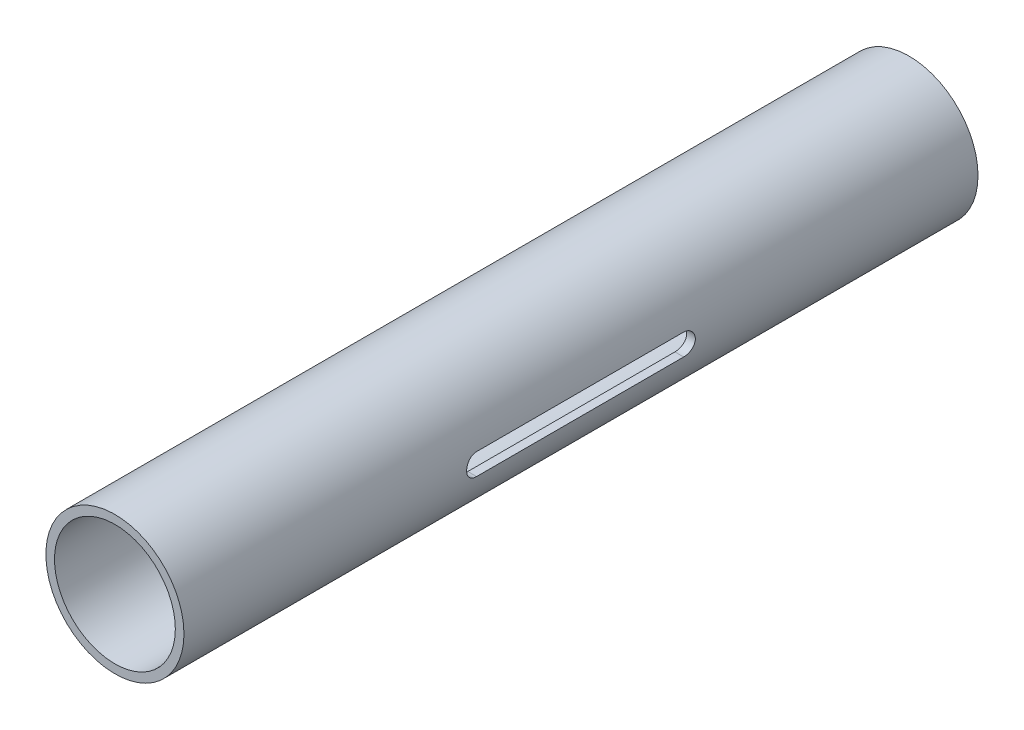
SolidWorks part; units mm, degrees
ref_plane "Front Plane" through (0, 0, 0) normal (0, 0, 1) x (1, 0, 0)
ref_plane "Top Plane" through (0, 0, 0) normal (0, 1, 0) x (1, 0, 0)
ref_plane "Right Plane" through (0, 0, 0) normal (1, 0, 0) x (0, 0, -1)
sketch "Sketch1" plane through (0, 0, 0) normal (0, 0, 1) x (1, 0, 0)
  line L0 (-25.4, 0) -> (-22.225, 0) construction
  circle A0 centre (0, 0) radius 22.225 construction
  circle A1 centre (0, 0) radius 25.4 construction
  dimension "OD" = 50.8
  dimension "ID" = 44.45
  dimension "Wall Thickness" = 3.175
sketch "Sketch2" plane through (0, 0, 0) normal (1, 0, 0) x (0, 0, -1)
  line L0 (-152.4, -25.4) -> (152.4, -25.4) construction
  point P2 (0, -25.4)
  point P3 (76.2, -25.4)
  point P4 (-76.2, -25.4)
  dimension "Length" = 304.8
  dimension "D1" = 76.2
  dimension "D2" = 76.2
sketch "Sketch3" plane through (0, 0, 0) normal (0, 0, 1) x (1, 0, 0)
  circle A0 centre (0, 0) radius 22.225 construction
  circle A1 centre (0, 0) radius 25.4 construction
  circle A2 centre (0, 0) radius 22.225
  circle A3 centre (0, 0) radius 25.4
extrude "Boss-Extrude2" add sketch "Sketch3" along normal up to vertex (152.4 mm away) and the other way up to vertex (152.4 mm away) up to point (0, -25.4, 152.4) other way up to point (0, -25.4, -152.4)
sketch "Sketch4" plane through (0, 0, 152.4) normal (0, 0, 1) x (1, 0, 0)
  circle A0 centre (0, 0) radius 36.4857
extrude "Cut-Extrude1" cut sketch "Sketch4" against normal offset from surface (12.7 mm away) 12.7 up to face at (25.4, 0, 152.4)
sketch "Sketch5" plane through (0, 0, 0) normal (1, 0, 0) x (0, 0, -1)
  line L0 (6.35, 0) -> (44.45, 0) construction
  line L1 (6.35, 0) -> (-31.75, 0) construction
  line L2 (-139.7, 0) -> (152.4, 0) construction
  line L3 (152.4, -25.4) -> (152.4, 25.4) construction
  line L4 (-139.7, 25.4) -> (-139.7, -25.4) construction
  line L5 (-31.75, 3.9687) -> (44.45, 3.9687)
  line L6 (44.45, -3.9687) -> (-31.75, -3.9687)
  line L7 (6.35, 3.9687) -> (6.35, -3.9687) construction
  circle A0 centre (-31.75, 0) radius 3.9687 construction
  arc A2 (-31.75, 3.9687) -> (-31.75, -3.9687) centre (-31.75, 0) ccw
  circle A4 centre (44.45, 0) radius 3.9688 construction
  arc A5 (44.45, 3.9687) -> (44.45, -3.9687) centre (44.45, 0) cw
  point P13 (6.35, 3.9687)
  point P14 (6.35, -3.9687)
  point P17 (6.35, 0)
  dimension "D1" = 38.1
  dimension "D2" = 107.95
  dimension "D3" = 7.9375
extrude "Cut-Extrude2" cut sketch "Sketch5" against normal through all both and the other way through all
equation "\"D1@Sketch2\"=\"OD@Sketch1\"*1.5"
equation "\"D2@Sketch2\"=\"D1@Sketch2\""
